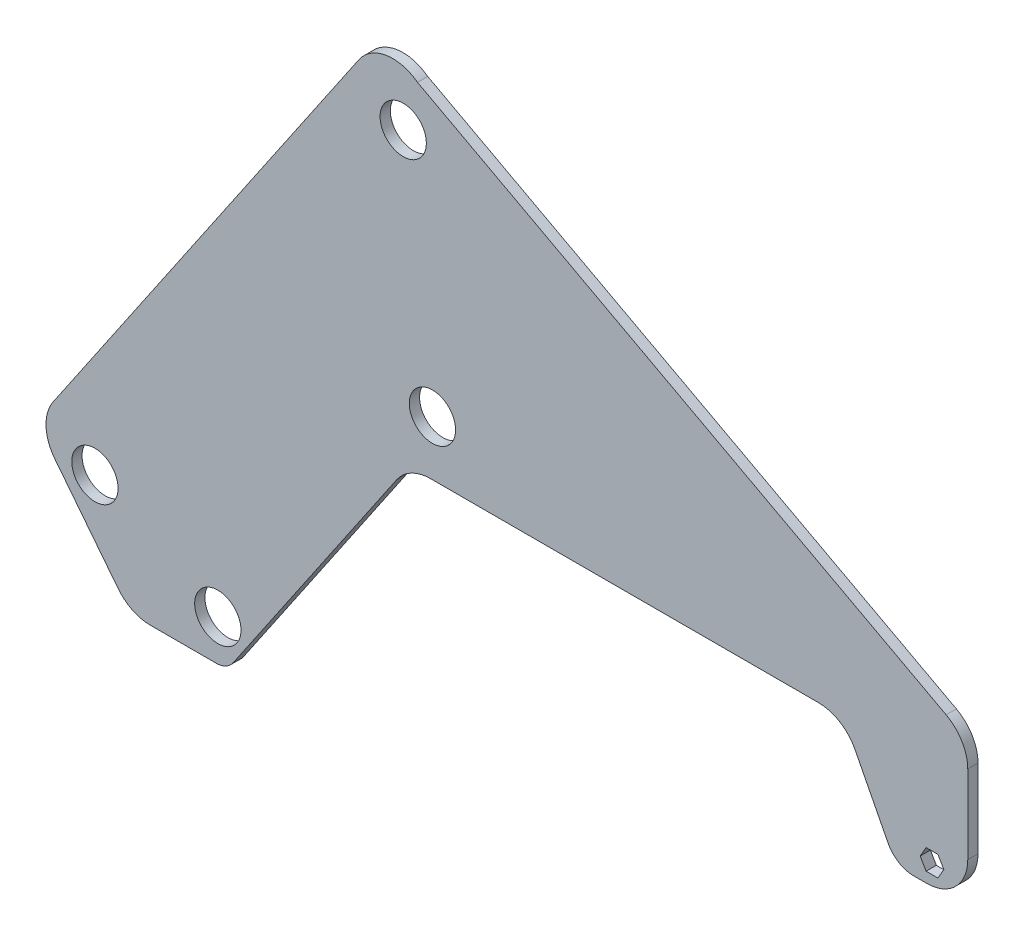
SolidWorks part; units mm, degrees
other "Markup1"
sketch "Sketch1" plane through (-441.7893, 331.8239, 6.35) normal (-0.0431, 0.0102, 0.999) x (0.9985, 0.0354, 0.0427)
sketch "Sketch2" plane through (-413.6701, 343.933, 6.35) normal (-0.0431, 0.0102, 0.999) x (0.9985, 0.0354, 0.0427)
sketch "Sketch3" plane through (-436.3774, 318.5567, 6.35) normal (-0.0431, 0.0102, 0.999) x (0.9985, 0.0354, 0.0427)
sketch "Sketch5" plane through (-436.3774, 318.5567, 6.35) normal (-0.0431, 0.0102, 0.999) x (0.9985, 0.0354, 0.0427)
sketch "Sketch7" plane through (-430.3226, 318.5567, 6.35) normal (-0.0431, 0.0102, 0.999) x (0.9985, 0.0354, 0.0427)
sketch "Sketch9" plane through (-430.3226, 318.5567, 6.35) normal (-0.0431, 0.0102, 0.999) x (0.9985, 0.0354, 0.0427)
sketch "Sketch11" plane through (-430.3226, 318.5567, 6.35) normal (-0.0431, 0.0102, 0.999) x (0.9985, 0.0354, 0.0427)
sketch "Sketch13" plane through (-430.3226, 318.5567, 6.35) normal (-0.0431, 0.0102, 0.999) x (0.9985, 0.0354, 0.0427)
other "Markup2"
sketch "Sketch4" plane through (102.4721, 318.5567, 6.35) normal (0.9364, 0.1073, 0.3342) x (0.3416, -0.0598, -0.9379)
sketch "Sketch6" plane through (102.4721, 318.5567, 6.35) normal (0.9364, 0.1073, 0.3342) x (0.3416, -0.0598, -0.9379)
sketch "Sketch8" plane through (141.2086, 318.5567, 6.35) normal (0.9364, 0.1073, 0.3342) x (0.3416, -0.0598, -0.9379)
sketch "Sketch10" plane through (141.2086, 318.5567, 6.35) normal (0.9364, 0.1073, 0.3342) x (0.3416, -0.0598, -0.9379)
sketch "Sketch12" plane through (141.2086, 318.5567, 6.35) normal (0.9364, 0.1073, 0.3342) x (0.3416, -0.0598, -0.9379)
sketch "Sketch14" plane through (141.2086, 318.5567, 6.35) normal (0.9364, 0.1073, 0.3342) x (0.3416, -0.0598, -0.9379)
material "Lexan"
ref_plane "Front Plane" through (0, 0, 0) normal (0, 0, 1) x (1, 0, 0)
ref_plane "Top Plane" through (0, 0, 0) normal (0, 1, 0) x (1, 0, 0)
ref_plane "Right Plane" through (0, 0, 0) normal (1, 0, 0) x (0, 0, -1)
sketch "Model" plane through (0, 0, 0) normal (0, 0, 1) x (1, 0, 0)
  line L1 (-191.9011, 104.6502) -> (-112.96, 104.6502)
  line L3 (-314.2383, -55.3595) -> (-212.8994, 93.5413)
  line L4 (-236.3032, 307.4477) -> (-425.9209, 28.8361)
  line L5 (-424.8981, -1.1437) -> (-385.5815, -51.2028)
  line L13 (126.3831, 53.8502) -> (122.717, 60.2002)
  line L14 (122.717, 60.2002) -> (115.3846, 60.2002)
  line L15 (115.3846, 60.2002) -> (111.7185, 53.8502)
  line L16 (111.7185, 53.8502) -> (115.3846, 47.5002)
  line L17 (115.3846, 47.5002) -> (122.717, 47.5002)
  line L18 (122.717, 47.5002) -> (126.3831, 53.8502)
  line L19 (-365.606, -60.914) -> (-324.7375, -60.914)
  line L20 (-871.0211, -88.854) -> (370.1019, -88.854) construction
  line L22 (141.2086, 66.5502) -> (141.2086, 78.8846)
  line L27 (107.6196, 41.1502) -> (115.8086, 41.1502)
  line L28 (-399.9752, 2.586) -> (-323.7752, -35.514) construction
  line L29 (-323.7752, -35.514) -> (-190.7071, 138.5169) construction
  line L30 (-190.7071, 138.5169) -> (-208.8329, 283.4378) construction
  line L31 (-208.8329, 283.4378) -> (-399.9752, 2.586) construction
  line L32 (91.8004, 50.8135) -> (71.26, 90.8456)
  line L33 (48.6612, 104.6502) -> (-11.3966, 104.6502)
  line L34 (141.2086, 78.8846) -> (141.2086, 115.3033)
  line L35 (127.8091, 137.6897) -> (-86.3327, 252.4836)
  line L36 (-112.96, 104.6502) -> (-68.51, 104.6502)
  line L37 (-122.3008, 271.7648) -> (-85.2777, 251.9181)
  line L40 (-68.51, 104.6502) -> (-2.1388, 104.6502)
  line L41 (-122.3008, 271.7648) -> (-199.9496, 313.3896)
  arc A3 (121.2475, 59.8082) -> (121.352, 60.2002) centre (96.7586, 66.5502) ccw
  circle A9 centre (-323.7752, -35.514) radius 14.351
  circle A10 centre (-399.9752, 2.586) radius 14.351
  circle A12 centre (-190.7071, 138.5169) radius 14.351
  arc A15 (107.6196, 41.1502) -> (91.8004, 50.8135) centre (107.6196, 58.9302) cw
  arc A21 (-191.9011, 104.6502) -> (-212.8994, 93.5413) centre (-191.9011, 79.2502) ccw
  circle A22 centre (-208.8329, 283.4378) radius 14.351
  circle A24 centre (119.0508, 53.8502) radius 6.35 construction
  arc A31 (-324.7375, -60.914) -> (-314.2383, -55.3595) centre (-324.7375, -48.214) ccw
  arc A40 (114.7422, 48.6129) -> (115.0458, 48.9225) centre (96.7586, 66.5502) ccw
  arc A43 (115.8086, 41.1502) -> (141.2086, 66.5502) centre (115.8086, 66.5502) ccw
  arc A44 (-236.3032, 307.4477) -> (-199.9496, 313.3896) centre (-215.305, 293.1567) cw
  arc A45 (-365.606, -60.914) -> (-385.5815, -51.2028) centre (-365.606, -35.514) cw
  arc A46 (71.26, 90.8456) -> (48.6612, 104.6502) centre (48.6612, 79.2502) ccw
  arc A47 (141.2086, 115.3033) -> (127.8091, 137.6897) centre (115.8086, 115.3033) ccw
  arc A48 (-424.8981, -1.1437) -> (-425.9209, 28.8361) centre (-404.9226, 14.5451) cw
  ellipse E0 centre (-551.1692, 173.9527) end of major axis (-591.2054, 216.0961) minor radius 17.278
  point P31 (-177.5612, 330.9695)
  point P34 (100.2935, -12.8222)
  point P43 (-377.9543, -60.914)
  point P55 (96.7586, 41.1502)
  point P59 (174.831, 53.8502)
  point P60 (-205.3388, 104.6502)
  point P64 (-436.3774, 13.472)
  dimension "D3" = 38.1
  dimension "D4" = 104.6502
  dimension "D5" = 76.2
  dimension "D6" = 44.45
  dimension "D7" = 12.7
  dimension "D8" = 28.702
  dimension "D11" = 139.7
  dimension "D12" = 27.94
  dimension "D21" = 124.238
  dimension "D13" = 12.7
  dimension "D16" = 355.6
  dimension "D23" = 25.4
  dimension "D24" = 25.4
  dimension "D26" = 25.4
  dimension "D14" = 406.4
  dimension "D20" = 254
  dimension "D29" = 25.4
  dimension "D31" = 25.4
  dimension "D25" = 88.9
  dimension "D30" = 17.78
  dimension "D32" = 25.4
  dimension "D33" = 25.4
  dimension "D9" = 19.05
  dimension "D10" = 146.05
  dimension "D15" = 33.8667
  dimension "D17" = 339.725
  dimension "D18" = 219.075
  dimension "D19" = 50.8
  dimension "D22" = 25.4
  dimension "D27" = 53.2168
  dimension "D28" = 12.7
extrude "Boss-Extrude1" add sketch "Model" along normal blind 6.35 contours L5 L3 L1 L4 A22 A9 A10 A12 region at (-206.9871, 107.7659, 0)
